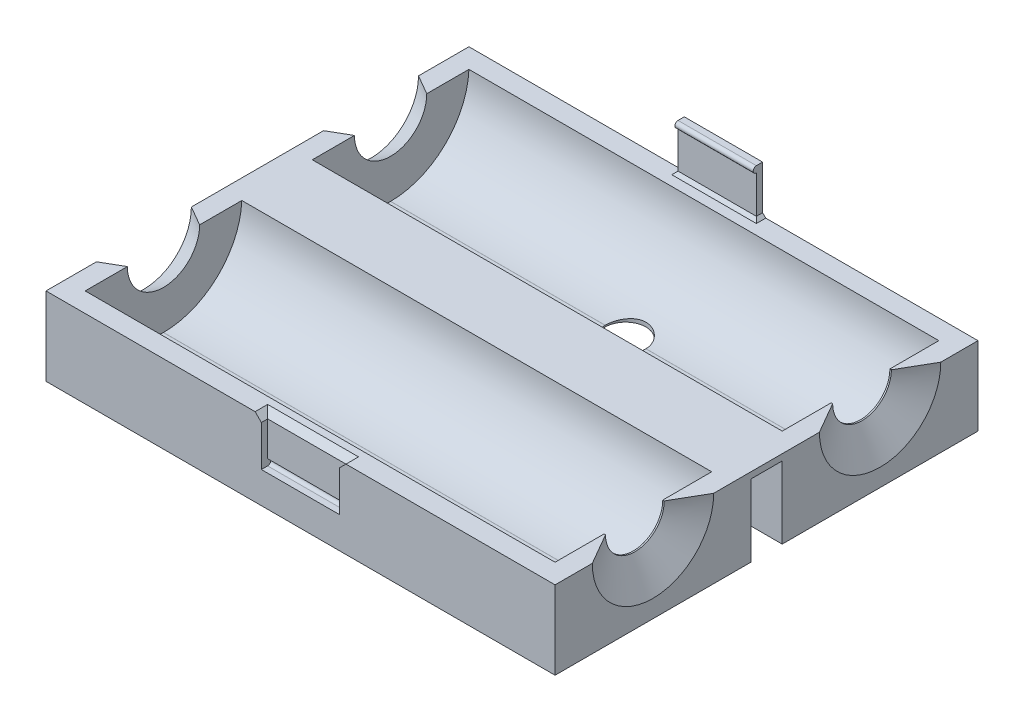
SolidWorks part; units mm, degrees
note: The reader was unsure of these and kept them because the rebuilt part matched: shared geometry of "Sketch1<3>", "Sketch1<5>", "Sketch6<5>".
ref_plane "Front Plane" through (0, 0, 0) normal (0, 0, 1) x (1, 0, 0)
ref_plane "Top Plane" through (0, 0, 0) normal (0, 1, 0) x (1, 0, 0)
ref_plane "Right Plane" through (0, 0, 0) normal (1, 0, 0) x (0, 0, -1)
sketch "Sketch1" plane through (0, 0, 0) normal (0, 1, 0) x (1, 0, 0)
  line L0 (-1.5875, -1.5875) -> (39.6875, -1.5875)
  line L1 (0, 0) -> (38.1, 0)
  line L2 (0, 0) -> (0, 12.7)
  line L3 (0, 12.7) -> (38.1, 12.7)
  line L4 (38.1, 0) -> (38.1, 12.7)
  line L5 (39.6875, -2.8575) -> (39.6875, 14.2875)
  line L6 (-1.5875, 14.2875) -> (39.6875, 14.2875)
  line L7 (-1.5875, -2.8575) -> (-1.5875, 14.2875)
  line L8 (-1.5875, -2.8575) -> (39.6875, -2.8575)
  line L9 (-1.5875, -2.8575) -> (-1.5875, -20.0025)
  line L10 (-1.5875, -20.0025) -> (39.6875, -20.0025)
  line L11 (39.6875, -2.8575) -> (39.6875, -20.0025)
  line L12 (38.1, -5.715) -> (38.1, -18.415)
  line L13 (0, -18.415) -> (38.1, -18.415)
  line L14 (0, -5.715) -> (0, -18.415)
  line L15 (0, -5.715) -> (38.1, -5.715)
  line L16 (-1.5875, -4.1275) -> (39.6875, -4.1275)
  line L17 (-1.5875, -1.5875) -> (-1.5875, 14.2875) construction
  line L18 (39.6875, -1.5875) -> (39.6875, 14.2875) construction
  line L19 (0, -12.065) -> (-1.5875, -12.065)
  line L20 (38.1, -12.065) -> (39.6875, -12.065)
  line L21 (0, 6.35) -> (-1.5875, 6.35)
  line L22 (38.1, 6.35) -> (39.6875, 6.35)
  dimension "D1" = 38.1
  dimension "D2" = 12.7
  dimension "D3" = 1.5875
  dimension "D4" = 1.27
extrude "Boss-Extrude1" add sketch "Sketch1" against normal blind 6.35 contours L22 L4 L1 L2 L21 L7 L0 L5 | L12 L20 L11 L16 L9 L19 L14 L15 | L20 L12 L13 L14 L19 L9 L10 L11 | L4 L22 L5 L6 L7 L21 L2 L3
extrude "Boss-Extrude2" add sketch "Sketch1<3>" against normal blind 1.5875 from offset 6.096 contours L15 L14 L13 L12 | L1 L4 L3 L2 offset against normal yes
sketch "Sketch1<3>" plane through (0, 0, 0) normal (0, 1, 0) x (1, 0, 0) same geometry as "Sketch1"
extrude "Boss-Extrude4" add sketch "Sketch1<5>" against normal blind 0.508 contours L7 L8 L5 L0 | L9 L16 L11 L8
sketch "Sketch1<5>" plane through (0, 0, 0) normal (0, 1, 0) x (1, 0, 0) same geometry as "Sketch1"
chamfer "Chamfer2" distance 1.524 angle 45 8 edges at (19.05, -6.35, 18.415) (0, -6.35, 12.065) (38.1, -6.35, 12.065) (19.05, -6.35, 5.715) (19.05, -6.35, 0) (38.1, -6.35, -6.35) (0, -6.35, -6.35) (19.05, -6.35, -12.7)
sketch "Sketch5" plane through (39.6875, 0, 0) normal (1, 0, 0) x (0, 0, -1)
  line L0 (-5.715, 0) -> (-18.415, 0) construction
  circle A0 centre (-12.065, 0) radius 2.3813
  circle A1 centre (6.35, 0) radius 2.3813
  point P0 (6.35, 0)
  point P2 (-12.065, 0)
  dimension "D1" = 4.7625
extrude "Cut-Extrude1" cut sketch "Sketch5" against normal through all
chamfer "Chamfer3" distance 2.54 angle 30 4 edges at (-1.5875, -2.3812, 12.065) (-1.5875, -2.3812, -6.35) (39.6875, -2.3812, -6.35) (39.6875, -2.3812, 12.065)
sketch "Sketch6" plane through (0, 0, 0) normal (0, 1, 0) x (1, 0, 0)
  line L0 (22.225, 13.7795) -> (22.225, 14.2875) construction
  line L1 (19.05, 13.2715) -> (19.05, 14.2875) construction
  line L2 (-1.5875, 14.2875) -> (39.6875, 14.2875) construction
  line L3 (19.05, 13.7795) -> (15.875, 13.7795) construction
  line L5 (12.7022, 14.2875) -> (15.875, 14.2875) construction
  line L6 (15.875, 13.7795) -> (15.875, 14.2875) construction
  line L7 (25.3978, 14.2875) -> (22.225, 14.2875) construction
  line L9 (19.05, 13.7795) -> (22.225, 13.7795) construction
  line L10 (-1.5875, -2.8575) -> (39.6875, -2.8575) construction
  line L11 (15.875, 14.2875) -> (22.225, 14.2875)
  line L12 (15.875, 14.2875) -> (15.875, 13.7795)
  line L13 (15.875, 13.7795) -> (22.225, 13.7795)
  line L14 (22.225, 14.2875) -> (22.225, 13.7795)
  line L15 (-1.5875, -2.8575) -> (39.6875, -2.8575)
  line L16 (19.05, -19.4945) -> (22.225, -19.4945) construction
  line L17 (25.3978, -20.0025) -> (22.225, -20.0025) construction
  line L18 (15.875, -19.4945) -> (15.875, -20.0025) construction
  line L19 (12.7022, -20.0025) -> (15.875, -20.0025) construction
  line L20 (19.05, -19.4945) -> (15.875, -19.4945) construction
  line L21 (19.05, -18.9865) -> (19.05, -20.0025) construction
  line L22 (22.225, -19.4945) -> (22.225, -20.0025) construction
  line L23 (22.225, -20.0025) -> (22.225, -19.4945)
  line L24 (15.875, -19.4945) -> (22.225, -19.4945)
  line L25 (15.875, -20.0025) -> (15.875, -19.4945)
  line L26 (15.875, -20.0025) -> (22.225, -20.0025)
  dimension "D1" = 6.35
  dimension "D2" = 0.508
extrude "Boss-Extrude7" add sketch "Sketch6" along direction (0, 1, 0) on the side of the normal blind 3.81
sketch "Sketch11" plane through (22.225, 0, 0) normal (1, 0, 0) x (0, 0, -1)
  line L0 (13.7795, 3.81) -> (13.7795, 0) construction
  line L1 (13.7795, 3.81) -> (13.7795, 3.302)
  arc A0 (13.7795, 3.81) -> (13.7795, 3.302) centre (13.7795, 3.556) ccw
  dimension "D1" = 0.254
extrude "Boss-Extrude10" add sketch "Sketch11" against normal up to surface (6.35 mm away) up to face at (15.875, 1.905, -14.0335)
extrude "Cut-Extrude2" cut sketch "Sketch6<5>" against normal blind 3.81 contours L25 L26 L23 L24
sketch "Sketch6<5>" plane through (0, 0, 0) normal (0, 1, 0) x (1, 0, 0) same geometry as "Sketch6"
sketch "Sketch9" plane through (22.225, 0, 0) normal (-1, 0, 0) x (0, 0, 1)
  line L0 (19.4945, -3.81) -> (19.4945, 0) construction
  line L1 (19.4945, -3.81) -> (19.4945, -3.302)
  arc A0 (19.4945, -3.81) -> (19.4945, -3.302) centre (19.4945, -3.556) cw
  dimension "D1" = 0.254
extrude "Cut-Extrude3" cut sketch "Sketch9" along normal up to surface (6.35 mm away) up to face at (15.875, -1.905, 19.7485)
chamfer "Chamfer4" distance 0.508 angle 45 3 edges at (15.875, 0, 19.7485) (19.05, 0, 19.4945) (22.225, 0, 19.7485)
chamfer "Chamfer5" distance 0.254 angle 45 3 edges at (15.875, 0, -14.0335) (22.225, 0, -14.0335) (19.05, 0, -13.7795)
sketch "Sketch10" plane through (0, -7.6835, 0) normal (0, -1, 0) x (1, 0, 0)
  line L0 (38.2905, -12.8905) -> (-0.1905, 0.1905)
  line L1 (-0.1905, -12.8905) -> (38.2905, 0.1905)
  circle A0 centre (19.05, -6.35) radius 1.651
  dimension "D1" = 3.302
extrude "Cut-Extrude4" cut sketch "Sketch10" against normal through all contours A0
chamfer "Chamfer6" distance 2.54 angle 30 1 edges at (19.05, -7.6835, -8.001)
fillet "Fillet1" radius 6.35 4 edges at (19.05, -6.096, 0) (19.05, -6.096, -12.7) (19.05, -6.096, 5.715) (19.05, -6.096, 18.415)
